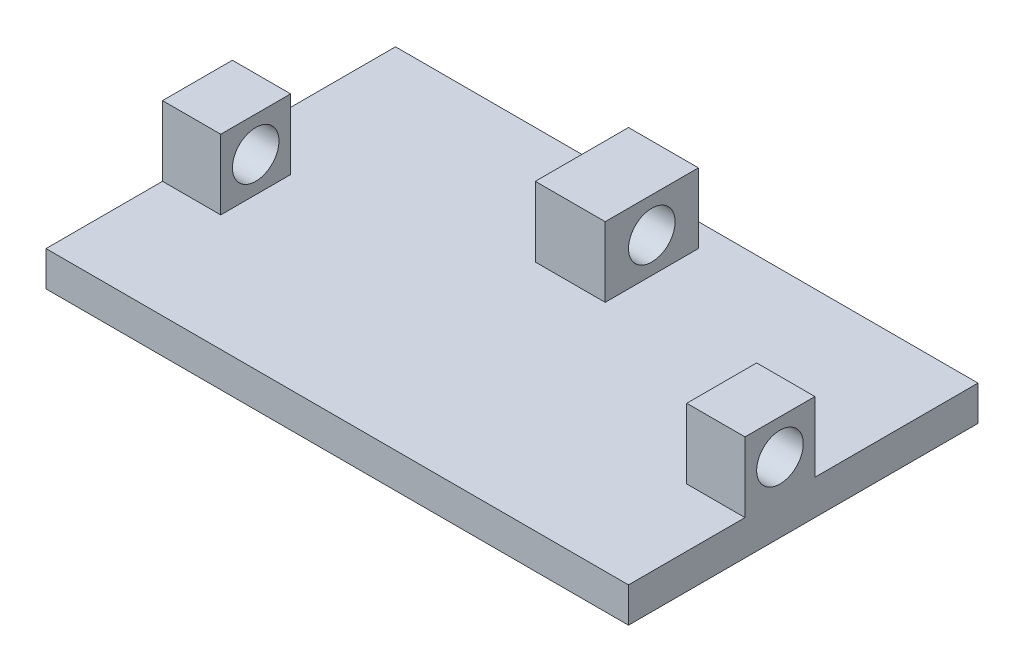
SolidWorks part; units mm, degrees
ref_plane "Front Plane" through (0, 0, 0) normal (0, 0, 1) x (1, 0, 0)
ref_plane "Top Plane" through (0, 0, 0) normal (0, 1, 0) x (1, 0, 0)
ref_plane "Right Plane" through (0, 0, 0) normal (1, 0, 0) x (0, 0, -1)
sketch "Sketch1" plane through (0, 0, 0) normal (0, 1, 0) x (1, 0, 0)
  line L0 (3, 15) -> (25, 15)
  line L1 (-25, 15) -> (-3, 15)
  line L2 (-25, 15) -> (-25, -15)
  line L3 (-25, -15) -> (25, -15)
  line L4 (25, 15) -> (25, -15)
  line L5 (-25, 15) -> (25, -15) construction
  line L6 (-25, -15) -> (25, 15) construction
  line L7 (-3, 5) -> (3, 5)
  line L8 (-3, 5) -> (-3, 13)
  line L9 (0, 10) -> (0, 0) construction
  line L10 (3, 5) -> (3, 13)
  line L11 (-3, 5) -> (3, 15) construction
  line L12 (-3, 15) -> (3, 5) construction
  line L13 (-3, 15) -> (3, 15)
  line L14 (3, 13) -> (-3, 13)
  point P0 (0, 0)
  point P6 (0, 10)
  dimension "D1" = 50
  dimension "D2" = 6
  dimension "D3" = 10
  dimension "D4" = 30
  dimension "D5" = 2
extrude "Boss-Extrude1" add sketch "Sketch1" along normal blind 3
sketch "Sketch3" plane through (0, 3, 0) normal (0, 1, 0) x (1, 0, 0)
  line L0 (-25, 15) -> (-25, -15) construction
  line L1 (-25, 1) -> (-20, 1)
  line L2 (-25, 1) -> (-25, -5)
  line L3 (-25, -5) -> (-20, -5)
  line L4 (-20, 1) -> (-20, -5)
  line L5 (25, -15) -> (25, 15) construction
  line L6 (25, 1) -> (20, 1)
  line L7 (25, 1) -> (25, -5)
  line L8 (25, -5) -> (20, -5)
  line L9 (20, 1) -> (20, -5)
  line L10 (-25, -15) -> (25, -15) construction
  dimension "D1" = 5
  dimension "D2" = 6
  dimension "D3" = 10
extrude "Boss-Extrude3" add sketch "Sketch3" along normal blind 6
sketch "Sketch4" plane through (-25, 0, 0) normal (-1, 0, 0) x (0, 0, 1)
  line L0 (-1, 3) -> (5, 9) construction
  circle A0 centre (2, 6) radius 2
  dimension "D1" = 4
extrude "Cut-Extrude1" cut sketch "Sketch4" against normal through all
sketch "Sketch5" plane through (0, 3, 0) normal (0, 1, 0) x (-1, 0, 0)
  line L1 (-3, -13) -> (3, -13)
  line L2 (-3, -13) -> (-3, -5)
  line L3 (-3, -5) -> (3, -5)
  line L4 (3, -13) -> (3, -5)
extrude "Boss-Extrude4" add sketch "Sketch5" along normal blind 6 and the other way blind 3
sketch "Sketch6" plane through (-3, 0, 0) normal (-1, 0, 0) x (0, 0, 1)
  line L0 (-13, 9) -> (-5, 3) construction
  line L1 (-5, 3) -> (-5, 9) construction
  circle A0 centre (-9, 6) radius 2
  dimension "D1" = 4
extrude "Cut-Extrude2" cut sketch "Sketch6" against normal blind 6
